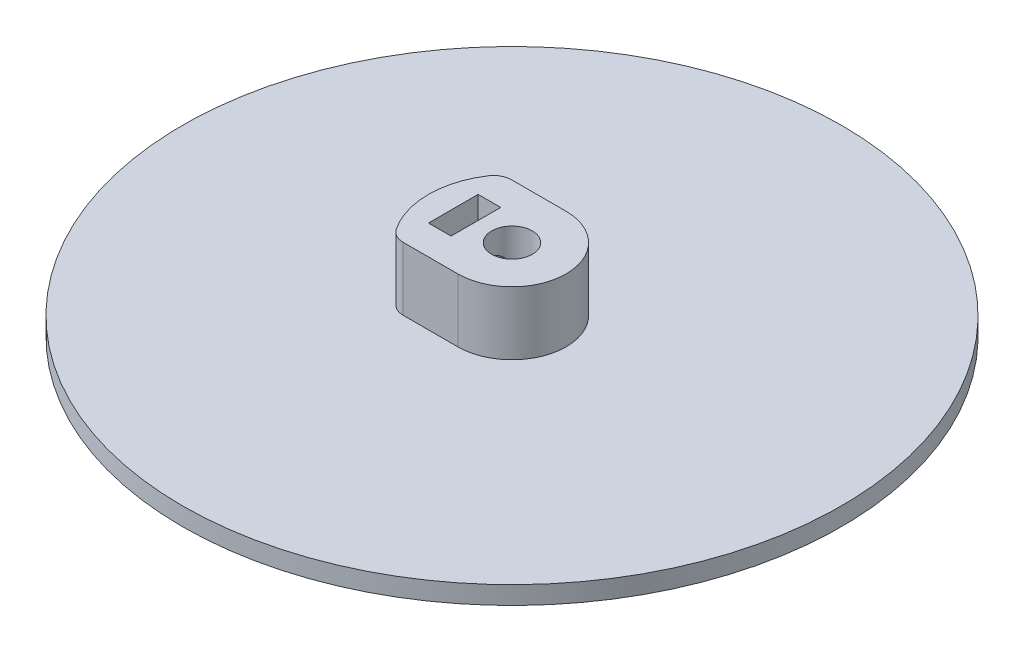
SolidWorks part; units mm, degrees
material "Custom Plastic"
ref_plane "Front Plane" through (0, 0, 0) normal (0, 0, 1) x (1, 0, 0)
ref_plane "Top Plane" through (0, 0, 0) normal (0, 1, 0) x (1, 0, 0)
ref_plane "Right Plane" through (0, 0, 0) normal (1, 0, 0) x (0, 0, -1)
sketch "Sketch1" plane through (0, 0, 0) normal (0, 1, 0) x (1, 0, 0)
  circle A0 centre (0, 0) radius 36.5
  dimension "D1" = 73
extrude "Boss-Extrude1" add sketch "Sketch1" along normal blind 5
sketch "Sketch2" plane through (0, 5, 0) normal (0, 1, 0) x (1, 0, 0)
  circle A0 centre (0, 0) radius 2.25
  circle A1 centre (0, 0) radius 9.25
  dimension "D1" = 4.5
  dimension "D2" = 7
extrude "Boss-Extrude2" add sketch "Sketch2" along normal blind 7
ref_plane "Plane1" through (-9.25, 0, 0) normal (-1, 0, 0) x (0, 0, 1)
hole_wizard "Ø1.0mm Dowel Hole1" positions "Sketch3" profile "Sketch4" hole size "Ø1.0" standard "ANSI Metric"
sketch "Sketch3" plane through (-9.25, 0, 0) normal (-1, 0, 0) x (0, 0, 1)
  line L0 (0, 12) -> (0, 5) construction
  line L1 (9.25, 12) -> (-9.25, 12) construction
  line L2 (36.5, 5) -> (-36.5, 5) construction
  point P0 (0, 8)
  dimension "D1" = 3
sketch "Sketch4" plane through (-9.25, 8, 0) normal (0, 1, 0) x (0, 0, 1)
  line L0 (0, 0) -> (0, 8)
  line L1 (0, 8) -> (1.5, 8)
  line L2 (1.5, 8) -> (1.5, 0)
  line L5 (1.5, 0) -> (0, 0)
  line L10 (0, 8) -> (-1.5, 8) construction
  line L11 (0, -6.35) -> (0, 107.95) construction
  dimension "Hole Dia." = 3
  dimension "Hole Depth" = 8
  dimension "Drill Angle" = 180
sketch "Sketch5" plane through (0, 5, 0) normal (0, 1, 0) x (1, 0, 0)
  circle A0 centre (0, 0) radius 2.25 construction
  circle A1 centre (0, 0) radius 2.25
extrude "Cut-Extrude1" cut sketch "Sketch5" against normal blind 2
ref_plane "Plane2" through (-6.5, 0, 0) normal (1, 0, 0) x (0, 0, -1)
sketch "Sketch6" plane through (-6.5, 0, 0) normal (1, 0, 0) x (0, 0, -1)
  line L0 (2.25, 12) -> (-2.25, 12) construction
  line L2 (-2.75, 12) -> (-2.75, 6.4123)
  line L3 (-2.75, 6.4123) -> (0, 4.8246)
  line L4 (0, 4.8246) -> (2.75, 6.4123)
  line L5 (2.75, 6.4123) -> (2.75, 12)
  line L7 (1.5915, 10.2566) -> (0.9665, 10.6174) [skipped]
  line L8 (-1.5915, 10.2566) -> (-2.2165, 9.8957) [skipped]
  line L9 (9.25, 12) -> (-9.25, 12) construction
  line L10 (-2.75, 12) -> (2.75, 12)
  circle A0 centre (0, 8) radius 2.75 construction
  dimension "D1" = 5.5
extrude "Cut-Extrude2" cut sketch "Sketch6" along normal blind 2.5
sketch "Sketch7" plane through (0, 12, 0) normal (0, 1, 0) x (1, 0, 0)
  line L0 (-7.0401, 6) -> (0, 6)
  line L1 (0, -6) -> (-7.0401, -6)
  circle A0 centre (0, 0) radius 9.25 construction
  arc A1 (0, 6) -> (0, -6) centre (0, 0) cw
  arc A2 (-7.0401, -6) -> (-7.0401, 6) centre (0, 0) ccw
  point P2 (0.3058, -5.9922)
  point P6 (0, 0)
  point P8 (0, 0)
  dimension "D1" = 6
extrude "Cut-Extrude3" cut sketch "Sketch7" against normal up to surface (7 mm away) up to face at (0, 5, 9.25)
fillet "Fillet1" radius 2 2 edges at (-7.0401, 8.5, -6) (-7.0401, 8.5, 6)
sketch "Sketch8" plane through (0, 0, 0) normal (0, -1, 0) x (1, 0, 0)
  circle A1 centre (0, 0) radius 36.5
  circle A2 centre (0, 0) radius 36.5
  dimension "D1" = 0
extrude "Cut-Extrude4" cut sketch "Sketch8" against normal blind 3
